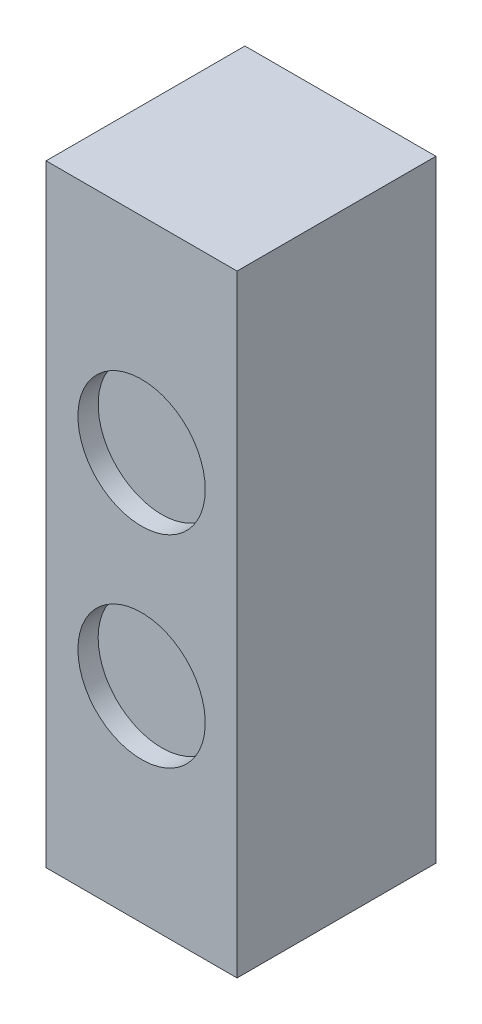
SolidWorks part; units mm, degrees
ref_plane "Front Plane" through (0, 0, 0) normal (0, 0, 1) x (1, 0, 0)
ref_plane "Top Plane" through (0, 0, 0) normal (0, 1, 0) x (1, 0, 0)
ref_plane "Right Plane" through (0, 0, 0) normal (1, 0, 0) x (0, 0, -1)
sketch "Sketch2" plane through (0, 0, 0) normal (0, 0, 1) x (1, 0, 0)
  line L1 (0, 0) -> (24.003, 0)
  line L2 (0, 0) -> (0, 76.962)
  line L3 (0, 76.962) -> (24.003, 76.962)
  line L4 (24.003, 0) -> (24.003, 76.962)
  dimension "D1" = 76.962
  dimension "D2" = 24.003
extrude "Boss-Extrude1" add sketch "Sketch2" along normal blind 24.9936
sketch "Sketch3" plane through (0, 0, 24.9936) normal (0, 0, 1) x (1, 0, 0)
  line L0 (12.0015, 76.962) -> (12.0015, 0) construction
  line L1 (24.003, 76.962) -> (0, 76.962) construction
  line L2 (0, 0) -> (24.003, 0) construction
  line L3 (0, 38.481) -> (24.003, 38.481) construction
  line L4 (0, 76.962) -> (0, 0) construction
  line L5 (24.003, 0) -> (24.003, 76.962) construction
  circle A0 centre (12.0015, 51.181) radius 8.001
  circle A2 centre (12.0015, 25.781) radius 8.001
  dimension "D1" = 16.002
  dimension "D2" = 12.7
extrude "Cut-Extrude1" cut sketch "Sketch3" against normal blind 2.54
sketch "Sketch4" plane through (0, 0, 24.9936) normal (0, 0, 1) x (1, 0, 0)
  line L0 (12.0015, 76.962) -> (12.0015, 0) construction
  line L1 (24.003, 76.962) -> (0, 76.962) construction
  line L2 (0, 0) -> (24.003, 0) construction
  line L3 (0, 38.481) -> (24.003, 38.481) construction
  line L4 (0, 76.962) -> (0, 0) construction
  line L5 (24.003, 0) -> (24.003, 76.962) construction
sketch "Sketch5" plane through (0, 0, 24.9936) normal (0, 0, 1) x (1, 0, 0)
  line L0 (12.0015, 76.962) -> (12.0015, 0) construction
  point P0 (12.0015, 38.481)
